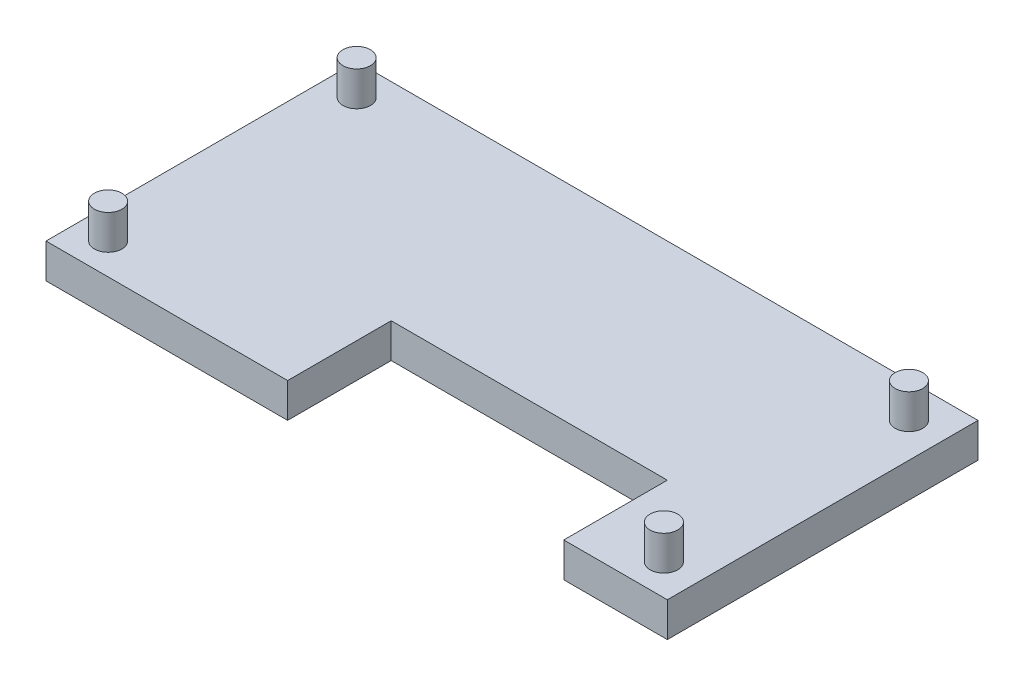
SolidWorks part; units mm, degrees
ref_plane "Front Plane" through (0, 0, 0) normal (0, 0, 1) x (1, 0, 0)
ref_plane "Top Plane" through (0, 0, 0) normal (0, 1, 0) x (1, 0, 0)
ref_plane "Right Plane" through (0, 0, 0) normal (1, 0, 0) x (0, 0, -1)
sketch "Sketch6" plane through (0, 0, 0) normal (0, 1, 0) x (1, 0, 0)
  line L1 (8.9128, 26.6643) -> (98.9128, 26.6643)
  line L2 (8.9128, 26.6643) -> (8.9128, -18.3357)
  line L3 (8.9128, -18.3357) -> (98.9128, -18.3357)
  line L4 (98.9128, 26.6643) -> (98.9128, -18.3357)
  line L5 (43.9128, -18.3357) -> (83.9128, -18.3357)
  line L6 (43.9128, -18.3357) -> (43.9128, -3.3357)
  line L7 (43.9128, -3.3357) -> (83.9128, -3.3357)
  line L8 (83.9128, -18.3357) -> (83.9128, -3.3357)
  circle A0 centre (13.4128, 22.1643) radius 2
  circle A1 centre (13.4128, -13.8357) radius 2
  circle A2 centre (93.9128, -13.8357) radius 2
  circle A3 centre (93.9128, 21.6643) radius 2
  dimension "D1" = 90
  dimension "D2" = 45
  dimension "D3" = 80.5
  dimension "D4" = 35.5
  dimension "D5" = 36
  dimension "D6" = 4.5
  dimension "D7" = 4.5
  dimension "D8" = 35
  dimension "D9" = 15
  dimension "D10" = 15
extrude "Boss-Extrude9" add sketch "Sketch6" along normal blind 5 separate body contours L8 L3 L4 L1 L2 L6 L7 A3 A2 A1 A0 | A3 | A2 | A1 | A0 region at (52.1517, 0, -6.8134) region at (13.4128, 0, 13.8357) region at (93.9128, 0, 13.8357) region at (93.9128, 0, -21.6643)
extrude "Boss-Extrude10" add sketch "Sketch6<3>" along normal blind 10 contours A0 | A3 | A2 | A1 region at (13.4128, 0, -22.1643) region at (93.9128, 0, -21.6643)
sketch "Sketch6<3>" plane through (0, 0, 0) normal (0, 1, 0) x (1, 0, 0) same geometry as "Sketch6"
